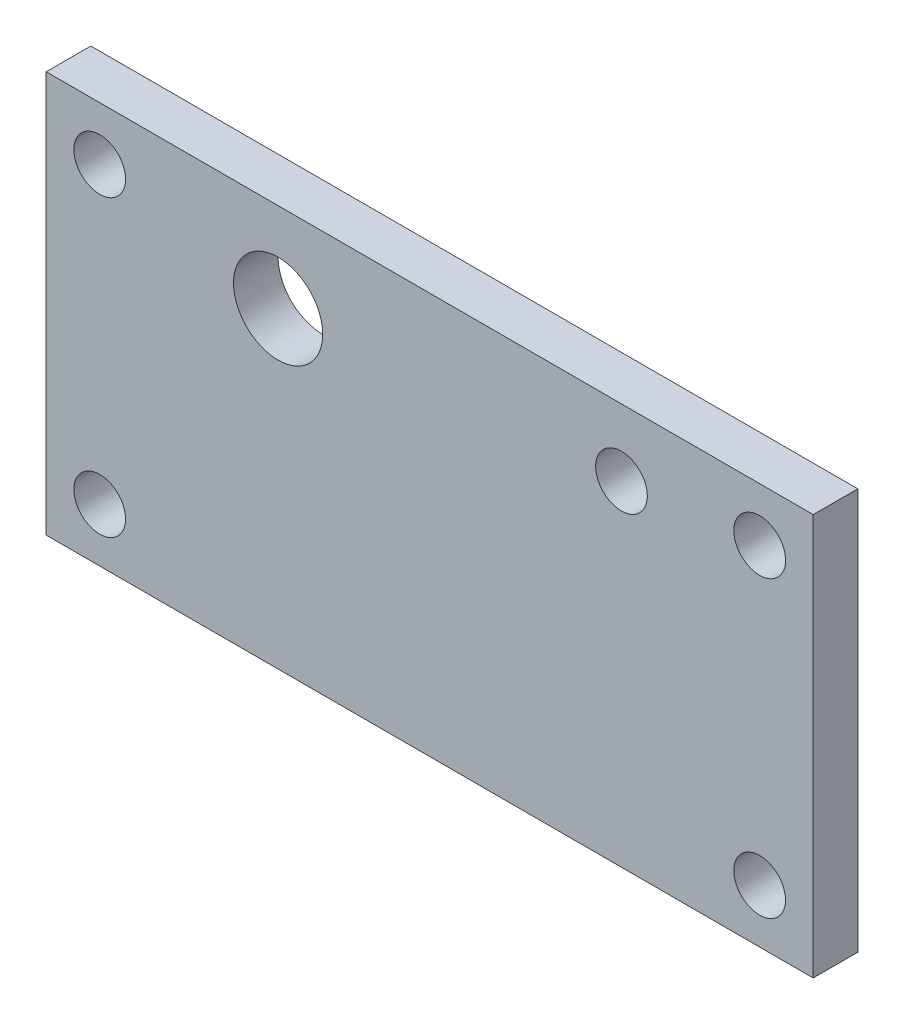
SolidWorks part; units mm, degrees
ref_plane "Front Plane" through (0, 0, 0) normal (0, 0, 1) x (1, 0, 0)
ref_plane "Top Plane" through (0, 0, 0) normal (0, 1, 0) x (1, 0, 0)
ref_plane "Right Plane" through (0, 0, 0) normal (1, 0, 0) x (0, 0, -1)
sketch "Sketch1" plane through (0, 0, 0) normal (0, 0, 1) x (1, 0, 0)
  line L1 (-27.305, 14.2875) -> (27.305, 14.2875)
  line L2 (-27.305, 14.2875) -> (-27.305, -14.2875)
  line L3 (-27.305, -14.2875) -> (27.305, -14.2875)
  line L4 (27.305, 14.2875) -> (27.305, -14.2875)
  line L5 (-27.305, 14.2875) -> (27.305, -14.2875) construction
  line L6 (-27.305, -14.2875) -> (27.305, 14.2875) construction
  circle A0 centre (-10.795, 7.9375) radius 3.175
  point P0 (0, 0)
  point P8 (0, 0)
  point P9 (0, 0)
  dimension "D4" = 6.35
  dimension "D1" = 28.575
  dimension "D2" = 54.61
  dimension "D3" = 6.35
  dimension "D5" = 38.1
extrude "Boss-Extrude1" add sketch "Sketch1" along normal blind 3.175
sketch "Sketch2" plane through (0, 0, 3.175) normal (0, 0, 1) x (1, 0, 0)
  line L0 (-27.305, 14.2875) -> (-27.305, -14.2875) construction
  line L1 (27.305, 14.2875) -> (-27.305, 14.2875) construction
  line L2 (-27.305, -14.2875) -> (27.305, -14.2875) construction
  line L3 (27.305, -14.2875) -> (27.305, 14.2875) construction
  circle A0 centre (-23.495, 10.4775) radius 1.8415
  circle A1 centre (-23.495, -10.4775) radius 1.8415
  circle A2 centre (23.495, -10.4775) radius 1.8415
  circle A3 centre (23.495, 10.4775) radius 1.8415
  point P8 (0, 0)
  point P9 (0, 0)
  point P10 (0, 0)
  point P11 (0, 0)
  dimension "D3" = 3.683
  dimension "D1" = 3.81
  dimension "D2" = 3.81
  dimension "D4" = 3.81
  dimension "D5" = 3.81
extrude "Cut-Extrude1" cut sketch "Sketch2" against normal through all
sketch "Sketch4" plane through (0, 0, 3.175) normal (0, 0, 1) x (1, 0, 0)
  line L0 (27.305, 14.2875) -> (-27.305, 14.2875) construction
  line L1 (27.305, -14.2875) -> (27.305, 14.2875) construction
  circle A0 centre (13.6525, 9.525) radius 1.8415
  point P6 (11.109, 8.9709)
  dimension "D3" = 3.683
  dimension "D1" = 4.7625
  dimension "D2" = 13.6525
extrude "Cut-Extrude2" cut sketch "Sketch4" against normal through all
